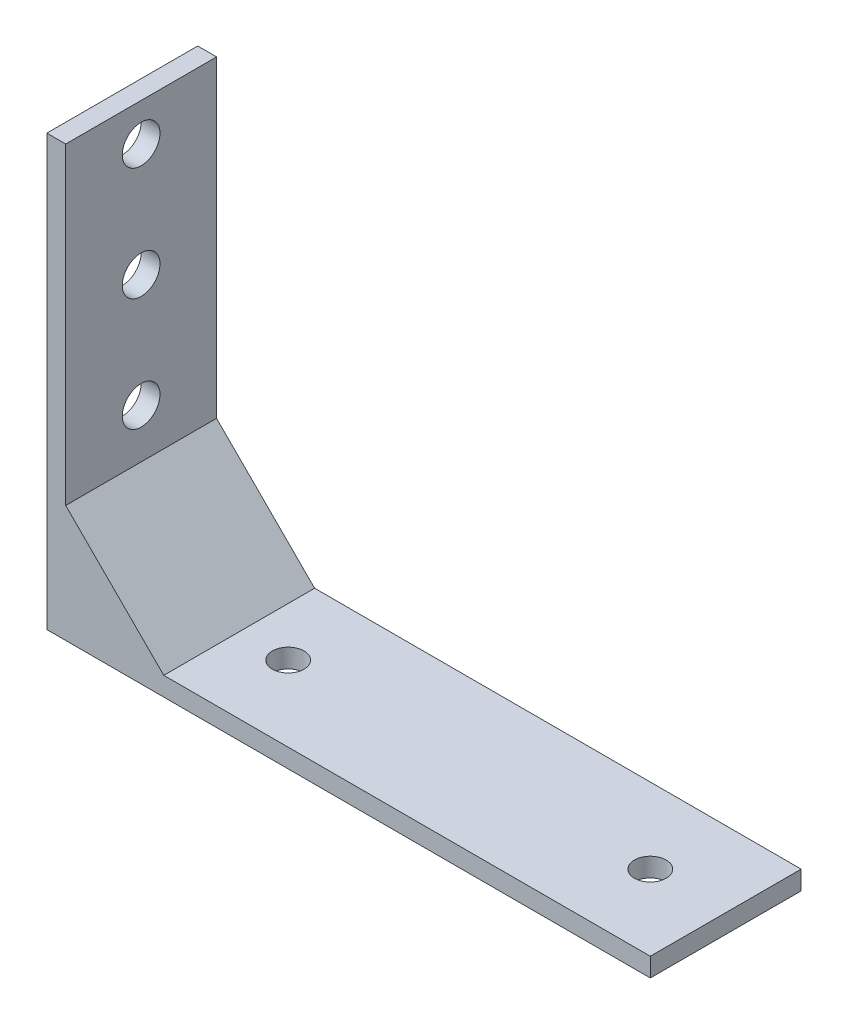
SolidWorks part; units mm, degrees
ref_plane "Front Plane" through (0, 0, 0) normal (0, 0, 1) x (1, 0, 0)
ref_plane "Top Plane" through (0, 0, 0) normal (0, 1, 0) x (1, 0, 0)
ref_plane "Right Plane" through (0, 0, 0) normal (1, 0, 0) x (0, 0, -1)
sketch "Sketch1" plane through (0, 0, 0) normal (0, 0, 1) x (1, 0, 0)
  line L1 (0, 0) -> (3.175, 0)
  line L2 (0, 0) -> (0, 72.39)
  line L3 (0, 72.39) -> (3.175, 72.39)
  line L4 (3.175, 3.175) -> (3.175, 72.39)
  line L5 (0, 0) -> (101.6, 0)
  line L6 (0, 0) -> (0, 3.175)
  line L7 (3.175, 3.175) -> (101.6, 3.175)
  line L8 (101.6, 0) -> (101.6, 3.175)
  dimension "D1" = 101.6
  dimension "D2" = 3.175
  dimension "D3" = 3.175
  dimension "D4" = 72.39
extrude "Boss-Extrude1" add sketch "Sketch1" along normal blind 25.4 contours L5 L8 L7 L4 L3 L2 L1 region at (1.2475, 1.5875, 0)
sketch "Sketch2" plane through (0, 3.175, 0) normal (0, 1, 0) x (1, 0, 0)
  line L0 (101.6, -25.4) -> (101.6, 0) construction
  line L1 (3.175, -25.4) -> (101.6, -25.4) construction
  circle A0 centre (88.9, -12.7) radius 2.667
  circle A1 centre (27.94, -12.7) radius 2.667
  dimension "D5" = 5.334
  dimension "D6" = 5.334
  dimension "D1" = 12.7
  dimension "D2" = 73.66
  dimension "D3" = 12.7
  dimension "D4" = 12.7
extrude "Cut-Extrude1" cut sketch "Sketch2" against normal blind 25.4
sketch "Sketch3" plane through (0, 0, 0) normal (-1, 0, 0) x (0, 0, 1)
  line L0 (25.4, 0) -> (0, 0) construction
  line L2 (0, 3.175) -> (0, 72.39) construction
  circle A0 centre (12.7, 27.94) radius 3.175
  circle A1 centre (12.7, 46.99) radius 3.175
  circle A2 centre (12.7, 66.04) radius 3.175
  point P10 (-9.6101, 68.6675)
  dimension "D1" = 6.35
  dimension "D2" = 6.35
  dimension "D3" = 6.35
  dimension "D4" = 27.94
  dimension "D5" = 19.05
  dimension "D6" = 19.05
  dimension "D7" = 12.7
  dimension "D8" = 12.7
  dimension "D9" = 12.7
extrude "Cut-Extrude2" cut sketch "Sketch3" against normal through all
sketch "Sketch4" plane through (0, 0, 25.4) normal (0, 0, 1) x (1, 0, 0)
  line L0 (3.175, 19.685) -> (19.685, 3.175)
  line L1 (3.175, 3.175) -> (3.175, 72.39) construction
  line L2 (3.175, 3.175) -> (101.6, 3.175) construction
  line L3 (19.685, 3.175) -> (3.175, 3.175)
  line L4 (3.175, 3.175) -> (3.175, 19.685)
  dimension "D1" = 45
  dimension "D2" = 16.51
extrude "Boss-Extrude2" add sketch "Sketch4" against normal blind 25.4
